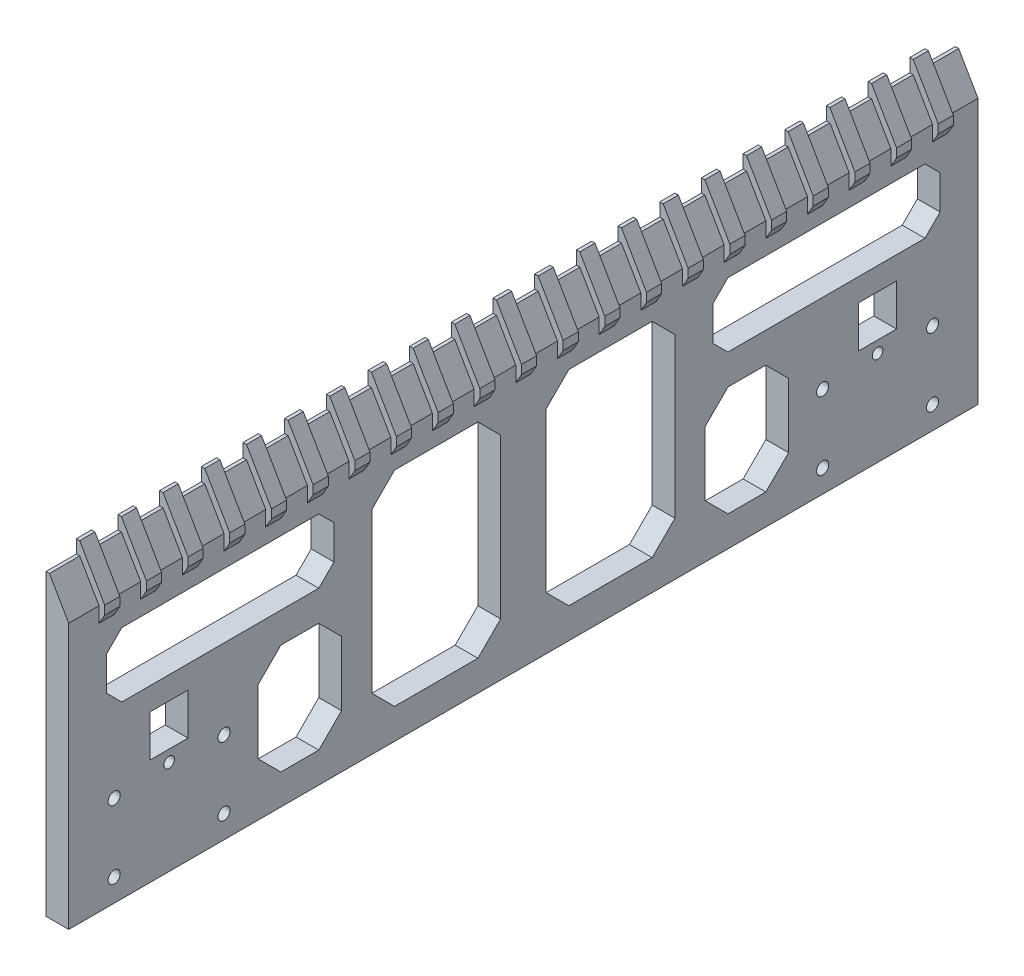
SolidWorks part; units mm, degrees
ref_plane "前视基准面" through (0, 0, 0) normal (0, 0, 1) x (1, 0, 0)
ref_plane "上视基准面" through (0, 0, 0) normal (0, 1, 0) x (1, 0, 0)
ref_plane "右视基准面" through (0, 0, 0) normal (1, 0, 0) x (0, 0, -1)
sketch "草图1" plane through (0, 0, 0) normal (1, 0, 0) x (0, 0, -1)
  line L1 (0, 0) -> (240, 0)
  line L2 (0, 0) -> (0, -70)
  line L3 (0, -70) -> (240, -70)
  line L4 (240, 0) -> (240, -70)
  dimension "D1" = 240
  dimension "D2" = 70
extrude "凸台-拉伸1" add sketch "草图1" along normal blind 6
sketch "草图3" plane through (6, 0, 0) normal (1, 0, 0) x (0, 0, -1)
  line L0 (120, 0) -> (120, -70) construction
  line L1 (14, -8) -> (66, -8)
  line L2 (10, -12) -> (10, -21)
  line L3 (14, -25) -> (66, -25)
  line L4 (70, -12) -> (70, -21)
  line L5 (240, 0) -> (0, 0) construction
  line L6 (0, -70) -> (240, -70) construction
  line L7 (0, 0) -> (0, -70) construction
  line L12 (10, -12) -> (14, -8)
  line L13 (10, -21) -> (14, -25)
  line L14 (66, -25) -> (70, -21)
  line L15 (66, -8) -> (70, -12)
  line L28 (80, -14) -> (86, -8)
  line L36 (50, -56) -> (56, -62)
  line L42 (86, -8) -> (108, -8)
  line L43 (80, -14) -> (80, -56)
  line L44 (86, -62) -> (108, -62)
  line L45 (114, -14) -> (114, -56)
  line L46 (108, -8) -> (114, -14)
  line L47 (108, -62) -> (114, -56)
  line L48 (80, -56) -> (86, -62)
  line L49 (56, -33) -> (66, -33)
  line L50 (50, -39) -> (50, -56)
  line L51 (56, -62) -> (66, -62)
  line L52 (72, -39) -> (72, -56)
  line L53 (66, -62) -> (72, -56)
  line L54 (66, -33) -> (72, -39)
  line L55 (50, -39) -> (56, -33)
  point P0 (10, -8)
  point P1 (70, -25)
  point P2 (10, -25)
  point P3 (70, -8)
  point P20 (80, -8)
  point P21 (114, -62)
  point P22 (80, -62)
  point P23 (114, -8)
  point P24 (50, -33)
  point P33 (72, -62)
  point P34 (50, -62)
  point P35 (72, -33)
  dimension "D1" = 10
  dimension "D2" = 8
  dimension "D3" = 17
  dimension "D4" = 60
  dimension "D5" = 8
  dimension "D6" = 8
  dimension "D7" = 54
  dimension "D12" = 80
  dimension "D13" = 6
  dimension "D14" = 34
  dimension "D15" = 10
  dimension "D16" = 8
  dimension "D21" = 8
  dimension "D22" = 29
  dimension "D23" = 22
extrude "切除-拉伸2" cut sketch "草图3" against normal through all
sketch "草图2" plane through (0, 0, 0) normal (1, 0, 0) x (0, 0, -1)
  line L0 (0, 0) -> (0, -70) construction
  line L1 (12, -46) -> (41, -46) construction
  line L2 (12, -46) -> (12, -64) construction
  line L3 (12, -64) -> (41, -64) construction
  line L4 (41, -46) -> (41, -64) construction
  line L5 (240, 0) -> (0, 0) construction
  line L6 (120, 0) -> (120, -70) construction
  circle A0 centre (12, -46) radius 1.55
  circle A1 centre (41, -64) radius 1.55
  circle A2 centre (41, -46) radius 1.55
  circle A3 centre (12, -64) radius 1.55
  dimension "D5" = 3.1
  dimension "D1" = 12
  dimension "D2" = 46
  dimension "D3" = 29
  dimension "D4" = 18
sketch "草图6" plane through (0, 0, 0) normal (0, 0, 1) x (1, 0, 0)
  line L0 (6, 0) -> (0, 0)
  line L1 (0, 0) -> (0, 8.8335)
  line L2 (0.9, 8.8335) -> (6, 0)
  line L3 (0, 8.8335) -> (0.9, 8.8335)
  line L4 (0, 8.8335) -> (0, 10.3923) construction
  line L5 (0, 10.3923) -> (0.9, 8.8335) construction
  dimension "D1" = 30
  dimension "D2" = 0.9
extrude "凸台-拉伸2" add sketch "草图6" against normal blind 240
ref_plane "基准面1" through (0, 0, -120) normal (0, 0, 1) x (1, 0, 0)
sketch "草图8" plane through (0, 0, -120) normal (0, 0, 1) x (1, 0, 0)
  line L0 (0, 10.3923) -> (0, 12.3335)
  line L1 (0.9, 12.3335) -> (7.5, 0.9019)
  line L2 (7.5, 0.9019) -> (7.5, -1.4019)
  line L3 (7.5, -4) -> (6, -4) construction
  line L4 (6, 0) -> (6, -70) construction
  line L5 (6, -4) -> (6, 0)
  line L6 (6, 0) -> (0.9, 8.8335) construction
  line L7 (6, 0) -> (0.9, 8.8335)
  line L8 (0, 12.3335) -> (0.9, 12.3335)
  line L9 (0, 12.3335) -> (0, 13.8923) construction
  line L10 (0, 13.8923) -> (0.9, 12.3335) construction
  line L11 (0, 10.3923) -> (0, 8.8335)
  line L12 (0, 8.8335) -> (0.9, 8.8335)
  line L13 (0.9, 8.8335) -> (0, 10.3923) construction
  line L14 (6, -4) -> (7.5, -1.4019)
  line L15 (7.5, -1.4019) -> (7.5, -4) construction
  dimension "D1" = 3.5
  dimension "D2" = 1.5
  dimension "D3" = 4
  dimension "D4" = 0.9
  dimension "D5" = 30
extrude "凸台-拉伸3" add sketch "草图8" along normal mid plane 4
pattern_linear "阵列(线性)1" count 11 spacing 11 along (0, 0, 1) count 11 spacing 11 along (0, 0, -1) of "凸台-拉伸3"
hole_wizard "打孔尺寸(%根据)内六角圆柱头螺钉的类型1" positions "草图14" profile "草图15" counterbore size "M3" standard "GB" end condition through all
sketch "草图14" plane through (0, 0, 0) normal (-1, 0, 0) x (0, 0, 1)
  point P0 (-41, -46)
  point P3 (-12, -46)
  point P6 (-12, -64)
  point P9 (-41, -64)
sketch "草图15" plane through (0, -46, -41) normal (0, 1, 0) x (0, 0, 1)
  line L0 (0, 0) -> (0, 7.5)
  line L1 (0, 7.5) -> (1.6, 7.5)
  line L3 (1.6, 7.5) -> (1.6, 3.4)
  line L4 (1.6, 3.4) -> (3, 3.4)
  line L5 (3, 3.4) -> (3, 0)
  line L7 (3, 0) -> (0, 0)
  line L11 (0, -6.35) -> (0, 107.95) construction
  dimension "通孔孔直径" = 3.2
  dimension "通孔孔深度" = 7.5
  dimension "柱形沉头孔直径" = 6
  dimension "柱形沉头孔深度" = 3.4
sketch "草图16" plane through (0, 0, 0) normal (-1, 0, 0) x (0, 0, 1)
  line L0 (-12, -46) -> (-41, -46) construction
  line L1 (-26.5, -46) -> (-26.5, -25) construction
  line L2 (-14, -25) -> (-66, -25) construction
  line L3 (-26.5, -46) -> (-26.5, -70) construction
  line L4 (0, -70) -> (-240, -70) construction
  circle A0 centre (-26.5, -45.0233) radius 1.4
  dimension "D1" = 2.8
extrude "切除-拉伸3" cut sketch "草图16" against normal blind 10
mirror "镜向1" about plane through (0, 0, -120) normal (0, 0, 1) of "打孔尺寸(%根据)内六角圆柱头螺钉的类型1"
mirror "镜向2" about plane through (0, 0, -120) normal (0, 0, 1) of "切除-拉伸3", "切除-拉伸2"
sketch "草图17" plane through (0, 0, 0) normal (-1, 0, 0) x (0, 0, 1)
  line L0 (0, 8.8335) -> (0, -70) construction
  line L1 (-31.5, -31) -> (-21.5, -31)
  line L2 (-31.5, -31) -> (-31.5, -42)
  line L3 (-31.5, -42) -> (-21.5, -42)
  line L4 (-21.5, -31) -> (-21.5, -42)
  line L6 (0, -70) -> (-240, -70) construction
  line L7 (-120, -70) -> (-120, -8.018) construction
  line L8 (-208.5, -31) -> (-218.5, -31)
  line L9 (-208.5, -31) -> (-208.5, -42)
  line L10 (-208.5, -42) -> (-218.5, -42)
  line L11 (-218.5, -31) -> (-218.5, -42)
  dimension "D1" = 10
  dimension "D2" = 11
  dimension "D3" = 21.5
  dimension "D4" = 28
extrude "切除-拉伸4" cut sketch "草图17" against normal through all
